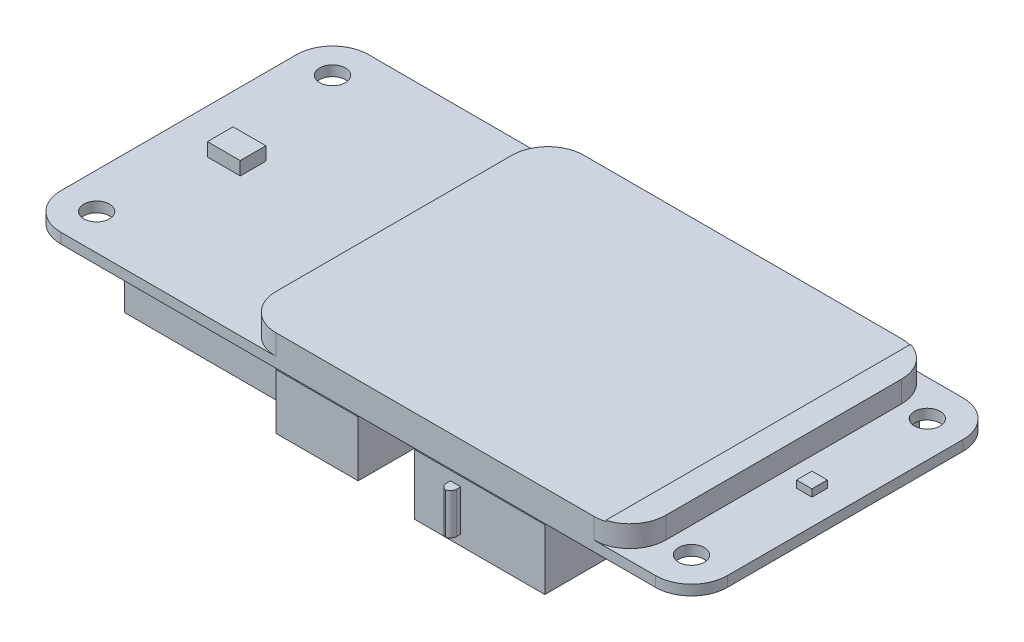
SolidWorks part; units mm, degrees
ref_plane "前视基准面" through (0, 0, 0) normal (0, 0, 1) x (1, 0, 0)
ref_plane "上视基准面" through (0, 0, 0) normal (0, 1, 0) x (1, 0, 0)
ref_plane "右视基准面" through (0, 0, 0) normal (1, 0, 0) x (0, 0, -1)
other "Configuration Table"
sketch "草图1" plane through (0, 0, 0) normal (0, 1, 0) x (1, 0, 0)
  line L1 (-29, 15) -> (29, 15)
  line L2 (-32.5, 11.5) -> (-32.5, -11.5)
  line L3 (-29, -15) -> (29, -15)
  line L4 (32.5, 11.5) -> (32.5, -11.5)
  line L5 (-32.5, 15) -> (32.5, -15) construction
  line L6 (-32.5, -15) -> (32.5, 15) construction
  arc A0 (29, -15) -> (32.5, -11.5) centre (29, -11.5) ccw
  arc A1 (29, 15) -> (32.5, 11.5) centre (29, 11.5) cw
  arc A2 (-32.5, -11.5) -> (-29, -15) centre (-29, -11.5) ccw
  arc A3 (-29, 15) -> (-32.5, 11.5) centre (-29, 11.5) ccw
  circle A4 centre (-29, 11.5) radius 1.25
  circle A5 centre (29, 11.5) radius 1.25
  circle A6 centre (-29, -11.5) radius 1.25
  circle A7 centre (29, -11.5) radius 1.25
  point P0 (0, 0)
  point P22 (-29.5, 12)
  dimension "D3" = 3.5
  dimension "D4" = 2.5
  dimension "D1" = 65
  dimension "D2" = 30
extrude "board" add sketch "草图1" along normal blind 1
sketch "草图2" plane through (0, 1, 0) normal (0, 1, 0) x (1, 0, 0)
  line L0 (29, 15) -> (-29, 15) construction
  line L1 (-11.5, 15) -> (26.5, 15)
  line L2 (-11.5, 15) -> (-11.5, -15)
  line L3 (-11.5, -15) -> (26.5, -15)
  line L4 (26.5, 15) -> (26.5, -15)
  line L5 (-29, -15) -> (29, -15) construction
  line L6 (-32.5, 11.5) -> (-32.5, -11.5) construction
  line L7 (32.5, -11.5) -> (32.5, 11.5) construction
  dimension "D1" = 6
  dimension "D2" = 21
extrude "screen" add sketch "草图2" along normal blind 2
fillet "screen-radius" radius 3.5 4 edges at (-11.5, 2, -15) (26.5, 2, -15) (26.5, 2, 15) (-11.5, 2, 15)
sketch "草图9" plane through (0, 3, 0) normal (0, 1, 0) x (1, 0, 0)
  line L0 (26.5, -11.5) -> (26.5, 11.5) construction
  line L1 (26.5, -11.5) -> (26.5, 11.5)
  line L2 (24, 14.8541) -> (24, -14.8541)
  line L3 (32.5, -11.5) -> (32.5, 11.5) construction
  arc A0 (23, -15) -> (26.5, -11.5) centre (23, -11.5) ccw construction
  arc A1 (26.5, 11.5) -> (23, 15) centre (23, 11.5) ccw construction
  arc A2 (26.5, -11.5) -> (24, -14.8541) centre (23, -11.5) cw
  arc A3 (26.5, 11.5) -> (24, 14.8541) centre (23, 11.5) ccw
  dimension "D1" = 8.5
extrude "screen-top" add sketch "草图9" along normal blind 0.1
sketch "草图3" plane through (0, 0, 0) normal (0, -1, 0) x (1, 0, 0)
  line L0 (32.5, 11.5) -> (32.5, -11.5) construction
  line L1 (-25.5, -9.25) -> (25.5, -9.25)
  line L2 (-25.5, -9.25) -> (-25.5, -14.25)
  line L3 (-25.5, -14.25) -> (25.5, -14.25)
  line L4 (25.5, -9.25) -> (25.5, -14.25)
  line L6 (29, -15) -> (-29, -15) construction
  dimension "D1" = 5
  dimension "D2" = 51
  dimension "D3" = 7
  dimension "D4" = 0.75
extrude "plug" add sketch "草图3" along normal blind 5.2
sketch "草图4" plane through (0, 0, 0) normal (0, -1, 0) x (1, 0, 0)
  line L1 (-25.09, 12.68) -> (-9.95, 12.68)
  line L2 (-25.09, 12.68) -> (-25.09, -7.32)
  line L3 (-25.09, -7.32) -> (-9.95, -7.32)
  line L4 (-9.95, 12.68) -> (-9.95, -7.32)
  line L5 (-32.5, -11.5) -> (-32.5, 11.5) construction
  line L6 (-29, 15) -> (29, 15) construction
  dimension "D1" = 15.14
  dimension "D2" = 20
  dimension "D3" = 7.41
  dimension "D4" = 2.32
extrude "speaker" add sketch "草图4" along normal blind 5
sketch "草图10" plane through (0, 0, 0) normal (0, -1, 0) x (1, 0, 0)
  line L0 (-29, 15) -> (29, 15) construction
  line L1 (-8, 15) -> (0, 15)
  line L2 (-8, 15) -> (-8, 9)
  line L3 (-8, 9) -> (0, 9)
  line L4 (0, 15) -> (0, 9)
  line L5 (-32.5, -11.5) -> (-32.5, 11.5) construction
  dimension "D1" = 8
  dimension "D2" = 6
  dimension "D3" = 24.5
extrude "speaker2plug" add sketch "草图10" along normal blind 5.5
sketch "草图5" plane through (0, 0, 0) normal (0, -1, 0) x (1, 0, 0)
  line L1 (5.5, 15) -> (18.2, 15)
  line L2 (5.5, 15) -> (5.5, 9)
  line L3 (5.5, 9) -> (18.2, 9)
  line L4 (18.2, 15) -> (18.2, 9)
  line L5 (-29, 15) -> (-8, 15) construction
  line L6 (32.5, 11.5) -> (32.5, -11.5) construction
  dimension "D1" = 12.7
  dimension "D2" = 6
  dimension "D4" = 14.3
extrude "button" add sketch "草图5" along normal blind 6
sketch "草图6" plane through (0, 0, 15) normal (0, 0, 1) x (1, 0, 0)
  line L1 (18.2, -6) -> (5.5, -6) construction
  line L3 (9, -1) -> (10, -1)
  line L4 (9, -1) -> (9, -5)
  line L5 (9, -5) -> (10, -5)
  line L6 (10, -1) -> (10, -5)
  line L7 (-29, 0) -> (-8, 0) construction
  dimension "D2" = 1
  dimension "D3" = 1
  dimension "D4" = 1
extrude "button-tap" add sketch "草图6" along normal blind 1
fillet "tap-radius " radius 0.6 2 edges at (10, -3, 16) (9, -3, 16)
sketch "草图7" plane through (0, 1, 0) normal (0, 1, 0) x (1, 0, 0)
  line L1 (28.5, 0.75) -> (30, 0.75)
  line L2 (28.5, 0.75) -> (28.5, -0.75)
  line L3 (28.5, -0.75) -> (30, -0.75)
  line L4 (30, 0.75) -> (30, -0.75)
  line L6 (32.5, -11.5) -> (32.5, 11.5) construction
  point P4 (32.5, 0)
  point P5 (30, 0)
  dimension "D1" = 1.5
  dimension "D2" = 1.5
  dimension "D4" = 2.5
extrude "rgb-led" add sketch "草图7" along normal blind 0.7
sketch "草图8" plane through (0, 1, 0) normal (0, 1, 0) x (1, 0, 0)
  line L0 (29, 15) -> (23, 15) construction
  line L1 (-25, 1) -> (-28.2, 1)
  line L2 (-25, 1) -> (-25, -1.5)
  line L3 (-25, -1.5) -> (-28.2, -1.5)
  line L4 (-28.2, 1) -> (-28.2, -1.5)
  line L6 (-32.5, 11.5) -> (-32.5, -11.5) construction
  dimension "D1" = 3.2
  dimension "D2" = 2.5
  dimension "D3" = 14
  dimension "D4" = 4.3
extrude "mic" add sketch "草图8" along normal blind 1.3
sketch "草图11" plane through (0, 0, 15) normal (0, 0, 1) x (1, 0, 0)
  line L0 (18.2, -6) -> (18.2, 0) construction
  line L1 (-8, 0) -> (18.2, 0)
  line L2 (-8, 0) -> (-8, -0.1)
  line L3 (-8, -0.1) -> (18.2, -0.1)
  line L4 (18.2, 0) -> (18.2, -0.1)
  line L5 (-8, -5.5) -> (-8, 0) construction
  point P7 (-8, -0.2777)
  point P10 (-8, 0)
  dimension "D1" = 0.1
extrude "split" cut sketch "草图11" against normal blind 1
